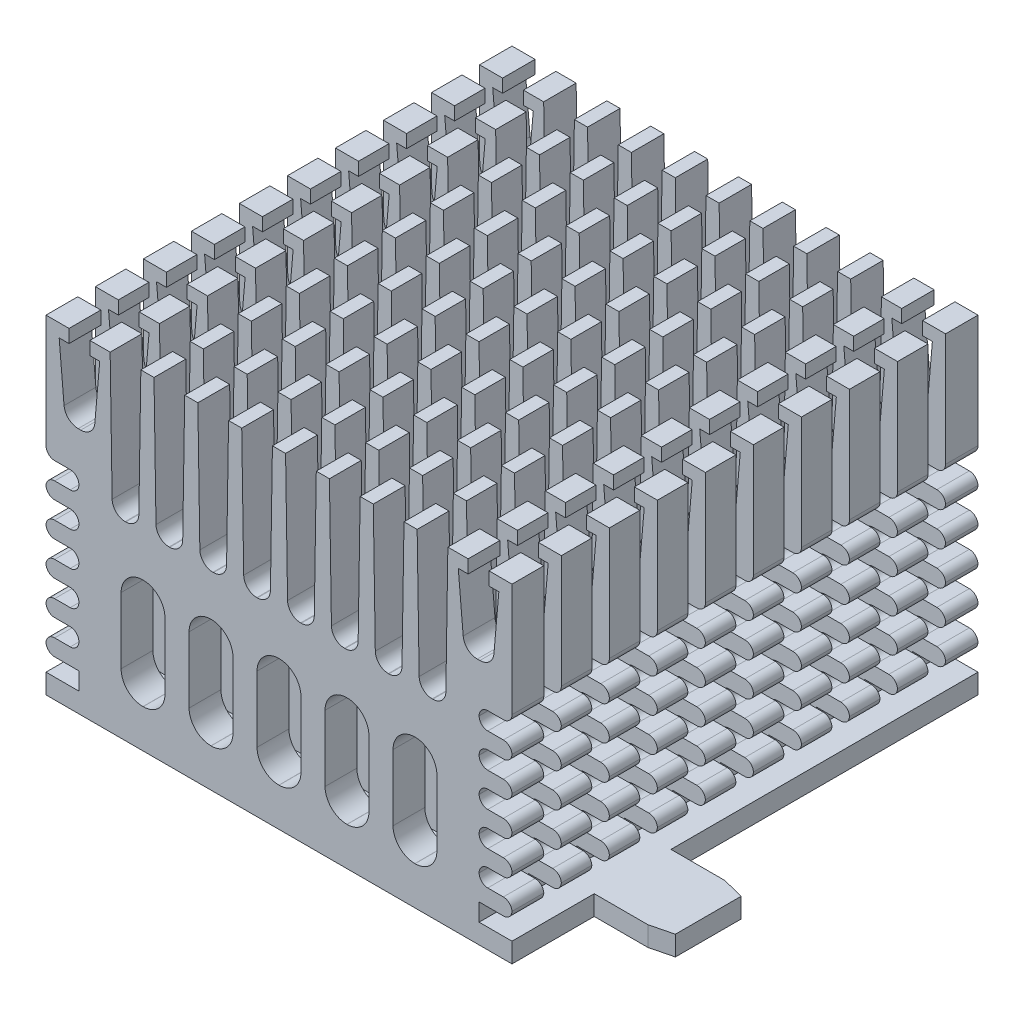
SolidWorks part; units mm, degrees
material "Aleación 1060"
ref_plane "Alzado" through (0, 0, 0) normal (0, 0, 1) x (1, 0, 0)
ref_plane "Planta" through (0, 0, 0) normal (0, 1, 0) x (1, 0, 0)
ref_plane "Vista lateral" through (0, 0, 0) normal (1, 0, 0) x (0, 0, -1)
sketch "Croquis3" plane through (0, 0, 0) normal (0, 1, 0) x (1, 0, 0)
  line L1 (-21.25, 21.25) -> (21.25, 21.25)
  line L2 (-21.25, 21.25) -> (-21.25, -21.25)
  line L3 (-21.25, -21.25) -> (21.25, -21.25)
  line L4 (21.25, 21.25) -> (21.25, -21.25)
  dimension "D1" = 42.5
  dimension "D2" = 42.5
  dimension "D3" = 21.25
  dimension "D4" = 21.25
extrude "Extruir1" add sketch "Croquis3" along normal blind 30
sketch "Croquis4" plane through (0, 0, 21.25) normal (0, 0, 1) x (1, 0, 0)
  line L0 (-19.15, 30) -> (-19.15, 28.8)
  line L1 (-21.25, 30) -> (21.25, 30) construction
  line L2 (-19.15, 28.8) -> (-20.05, 28.8)
  line L3 (-20.05, 28.8) -> (-19.6028, 23.6778)
  line L4 (-18.3177, 22.5) -> (-18.0823, 22.5)
  line L5 (-16.7972, 23.6778) -> (-16.35, 28.8)
  line L6 (-16.35, 28.8) -> (-17.25, 28.8)
  line L7 (-17.25, 28.8) -> (-17.25, 30)
  line L8 (-17.25, 30) -> (-19.15, 30)
  line L9 (-0.6, 30) -> (-0.7816, 18.4713)
  line L10 (-18.2, 30) -> (-18.2, 19.4356) construction
  line L11 (-21.25, 30) -> (-21.25, 0) construction
  line L12 (0, 30) -> (0, 39.1053) construction
  line L13 (-1.9714, 17.3) -> (-2.0286, 17.3)
  line L14 (17.25, 30) -> (19.15, 30)
  line L15 (17.25, 28.8) -> (17.25, 30)
  line L16 (16.35, 28.8) -> (17.25, 28.8)
  line L17 (16.7972, 23.6778) -> (16.35, 28.8)
  line L18 (18.3177, 22.5) -> (18.0823, 22.5)
  line L19 (20.05, 28.8) -> (19.6028, 23.6778)
  line L20 (19.15, 28.8) -> (20.05, 28.8)
  line L21 (19.15, 30) -> (19.15, 28.8)
  line L22 (-3.2184, 18.4713) -> (-3.4, 30)
  line L23 (-3.4, 30) -> (-0.6, 30)
  line L24 (-2, 30) -> (-2, 27.0397) construction
  line L25 (-4.6, 30) -> (-4.7816, 18.4713)
  line L26 (-5.9714, 17.3) -> (-6.0286, 17.3)
  line L27 (-7.2184, 18.4713) -> (-7.4, 30)
  line L28 (-7.4, 30) -> (-4.6, 30)
  line L29 (-6, 30) -> (-6, 27.0397) construction
  line L30 (-8.6, 30) -> (-8.7816, 18.4713)
  line L31 (-9.9714, 17.3) -> (-10.0286, 17.3)
  line L32 (-11.2184, 18.4713) -> (-11.4, 30)
  line L33 (-11.4, 30) -> (-8.6, 30)
  line L34 (-10, 30) -> (-10, 27.0397) construction
  line L35 (-12.6, 30) -> (-12.7816, 18.4713)
  line L36 (-13.9714, 17.3) -> (-14.0286, 17.3)
  line L37 (-15.2184, 18.4713) -> (-15.4, 30)
  line L38 (-15.4, 30) -> (-12.6, 30)
  line L39 (-14, 30) -> (-14, 27.0397) construction
  line L40 (14, 30) -> (14, 27.0397) construction
  line L41 (10, 30) -> (10, 27.0397) construction
  line L42 (6, 30) -> (6, 27.0397) construction
  line L43 (2, 30) -> (2, 27.0397) construction
  line L44 (15.4, 30) -> (12.6, 30)
  line L45 (15.2184, 18.4713) -> (15.4, 30)
  line L46 (13.9714, 17.3) -> (14.0286, 17.3)
  line L47 (12.6, 30) -> (12.7816, 18.4713)
  line L48 (11.4, 30) -> (8.6, 30)
  line L49 (11.2184, 18.4713) -> (11.4, 30)
  line L50 (9.9714, 17.3) -> (10.0286, 17.3)
  line L51 (8.6, 30) -> (8.7816, 18.4713)
  line L52 (7.4, 30) -> (4.6, 30)
  line L53 (7.2184, 18.4713) -> (7.4, 30)
  line L54 (5.9714, 17.3) -> (6.0286, 17.3)
  line L55 (4.6, 30) -> (4.7816, 18.4713)
  line L56 (3.4, 30) -> (0.6, 30)
  line L57 (3.2184, 18.4713) -> (3.4, 30)
  line L58 (1.9714, 17.3) -> (2.0286, 17.3)
  line L59 (0.6, 30) -> (0.7816, 18.4713)
  arc A0 (-19.6028, 23.6778) -> (-18.3177, 22.5) centre (-18.3177, 23.79) ccw
  arc A1 (-18.0823, 22.5) -> (-16.7972, 23.6778) centre (-18.0823, 23.79) ccw
  arc A2 (18.0823, 22.5) -> (16.7972, 23.6778) centre (18.0823, 23.79) cw
  arc A3 (19.6028, 23.6778) -> (18.3177, 22.5) centre (18.3177, 23.79) cw
  arc A4 (-0.7816, 18.4713) -> (-1.9714, 17.3) centre (-1.9714, 18.49) cw
  arc A5 (-2.0286, 17.3) -> (-3.2184, 18.4713) centre (-2.0286, 18.49) cw
  arc A6 (-4.7816, 18.4713) -> (-5.9714, 17.3) centre (-5.9714, 18.49) cw
  arc A7 (-6.0286, 17.3) -> (-7.2184, 18.4713) centre (-6.0286, 18.49) cw
  arc A8 (-8.7816, 18.4713) -> (-9.9714, 17.3) centre (-9.9714, 18.49) cw
  arc A9 (-10.0286, 17.3) -> (-11.2184, 18.4713) centre (-10.0286, 18.49) cw
  arc A10 (-12.7816, 18.4713) -> (-13.9714, 17.3) centre (-13.9714, 18.49) cw
  arc A11 (-14.0286, 17.3) -> (-15.2184, 18.4713) centre (-14.0286, 18.49) cw
  arc A12 (14.0286, 17.3) -> (15.2184, 18.4713) centre (14.0286, 18.49) ccw
  arc A13 (12.7816, 18.4713) -> (13.9714, 17.3) centre (13.9714, 18.49) ccw
  arc A14 (10.0286, 17.3) -> (11.2184, 18.4713) centre (10.0286, 18.49) ccw
  arc A15 (8.7816, 18.4713) -> (9.9714, 17.3) centre (9.9714, 18.49) ccw
  arc A16 (6.0286, 17.3) -> (7.2184, 18.4713) centre (6.0286, 18.49) ccw
  arc A17 (4.7816, 18.4713) -> (5.9714, 17.3) centre (5.9714, 18.49) ccw
  arc A18 (2.0286, 17.3) -> (3.2184, 18.4713) centre (2.0286, 18.49) ccw
  arc A19 (0.7816, 18.4713) -> (1.9714, 17.3) centre (1.9714, 18.49) ccw
  point P17 (-19.5, 22.5)
  point P20 (-16.9, 22.5)
  point P37 (16.9, 22.5)
  point P38 (19.5, 22.5)
  point P45 (-0.8, 17.3)
  point P48 (-3.2, 17.3)
  point P119 (3.2, 17.3)
  point P120 (0.8, 17.3)
  dimension "D9" = 1.29
  dimension "D15" = 1.19
  dimension "D1" = 1.9
  dimension "D2" = 3.7
  dimension "D3" = 1.85
  dimension "D4" = 1.2
  dimension "D5" = 7.5
  dimension "D6" = 2.6
  dimension "D7" = 1.3
  dimension "D8" = 2.1
  dimension "D10" = 2.8
  dimension "D11" = 2.4
  dimension "D12" = 1.2
  dimension "D13" = 12.7
  dimension "D14" = 0.6
extrude "Cortar-Extruir1" cut sketch "Croquis4" against normal blind 55
sketch "Croquis5" plane through (0, 0, 21.25) normal (0, 0, 1) x (1, 0, 0)
  line L0 (-21.25, 30) -> (-21.25, 0) construction
  line L1 (-21.8997, 18.9) -> (-18.25, 18.9)
  line L2 (-21.8997, 18.9) -> (-21.8997, 17.3)
  line L3 (-21.8997, 17.3) -> (-18.25, 17.3)
  line L4 (-18.25, 18.9) -> (-18.25, 17.3)
  line L5 (-21.8997, 15.8) -> (-18.25, 15.8)
  line L6 (-21.8997, 15.8) -> (-21.8997, 14.2)
  line L7 (-21.8997, 14.2) -> (-18.25, 14.2)
  line L8 (-18.25, 15.8) -> (-18.25, 14.2)
  line L9 (-21.8997, 12.7) -> (-18.25, 12.7)
  line L10 (-21.8997, 12.7) -> (-21.8997, 11.1)
  line L11 (-21.8997, 11.1) -> (-18.25, 11.1)
  line L12 (-18.25, 12.7) -> (-18.25, 11.1)
  line L13 (-21.8997, 9.6) -> (-18.25, 9.6)
  line L14 (-21.8997, 9.6) -> (-21.8997, 8)
  line L15 (-21.8997, 8) -> (-18.25, 8)
  line L16 (-18.25, 9.6) -> (-18.25, 8)
  line L17 (-21.8997, 6.5) -> (-18.25, 6.5)
  line L18 (-21.8997, 6.5) -> (-21.8997, 4.9)
  line L19 (-21.8997, 4.9) -> (-18.25, 4.9)
  line L20 (-18.25, 6.5) -> (-18.25, 4.9)
  line L21 (-21.8997, 3.4) -> (-18.25, 3.4)
  line L22 (-21.8997, 3.4) -> (-21.8997, 1.8)
  line L23 (-21.8997, 1.8) -> (-18.25, 1.8)
  line L24 (-18.25, 3.4) -> (-18.25, 1.8)
  line L25 (0, 0) -> (0, -4.9995) construction
  line L26 (18.25, 3.4) -> (18.25, 1.8)
  line L27 (21.8997, 1.8) -> (18.25, 1.8)
  line L28 (21.8997, 3.4) -> (21.8997, 1.8)
  line L29 (21.8997, 3.4) -> (18.25, 3.4)
  line L30 (18.25, 6.5) -> (18.25, 4.9)
  line L31 (21.8997, 4.9) -> (18.25, 4.9)
  line L32 (21.8997, 6.5) -> (21.8997, 4.9)
  line L33 (21.8997, 6.5) -> (18.25, 6.5)
  line L34 (18.25, 9.6) -> (18.25, 8)
  line L35 (21.8997, 8) -> (18.25, 8)
  line L36 (21.8997, 9.6) -> (21.8997, 8)
  line L37 (21.8997, 9.6) -> (18.25, 9.6)
  line L38 (18.25, 12.7) -> (18.25, 11.1)
  line L39 (21.8997, 11.1) -> (18.25, 11.1)
  line L40 (21.8997, 12.7) -> (21.8997, 11.1)
  line L41 (21.8997, 12.7) -> (18.25, 12.7)
  line L42 (18.25, 15.8) -> (18.25, 14.2)
  line L43 (21.8997, 14.2) -> (18.25, 14.2)
  line L44 (21.8997, 15.8) -> (21.8997, 14.2)
  line L45 (21.8997, 15.8) -> (18.25, 15.8)
  line L46 (18.25, 18.9) -> (18.25, 17.3)
  line L47 (21.8997, 17.3) -> (18.25, 17.3)
  line L48 (21.8997, 18.9) -> (21.8997, 17.3)
  line L49 (21.8997, 18.9) -> (18.25, 18.9)
  dimension "D1" = 3
  dimension "D2" = 1.6
  dimension "D3" = 1.5
extrude "Cortar-Extruir2" cut sketch "Croquis5" against normal blind 55
fillet "Redondeo1" radius 0.79 21 edges at (-21.25, 3.4, 0) (-21.25, 4.9, 0) (-18.25, 4.9, 0) (-18.25, 6.5, 0) (-21.25, 6.5, 0) (-21.25, 8, 0) (-18.25, 9.6, 0) (-18.25, 8, 0) (-21.25, 9.6, 0) (-21.25, 11.1, 0) (-18.25, 12.7, 0) (-18.25, 11.1, 0) (-21.25, 12.7, 0) (-21.25, 14.2, 0) (-18.25, 14.2, 0) (-18.25, 15.8, 0) (-21.25, 15.8, 0) (-21.25, 17.3, 0) (-21.25, 18.9, 0) (-18.25, 17.3, 0) (-18.25, 18.9, 0)
fillet "Redondeo2" radius 0.79 21 edges at (21.25, 3.4, 0) (21.25, 4.9, 0) (18.25, 4.9, 0) (18.25, 6.5, 0) (21.25, 6.5, 0) (21.25, 8, 0) (18.25, 8, 0) (18.25, 9.6, 0) (21.25, 9.6, 0) (21.25, 11.1, 0) (18.25, 11.1, 0) (18.25, 12.7, 0) (21.25, 12.7, 0) (21.25, 14.2, 0) (18.25, 14.2, 0) (18.25, 15.8, 0) (21.25, 15.8, 0) (21.25, 17.3, 0) (18.25, 17.3, 0) (18.25, 18.9, 0) (21.25, 18.9, 0)
sketch "Croquis7" plane through (0, 0, 21.25) normal (0, 0, 1) x (1, 0, 0)
  line L0 (0, 0) -> (0, -2.1081) construction
  line L1 (-0.01, 13.5) -> (0.01, 13.5)
  line L2 (-2, 11.51) -> (-2, 5.49)
  line L3 (-0.01, 3.5) -> (0.01, 3.5)
  line L4 (2, 11.51) -> (2, 5.49)
  line L5 (-21.25, 0) -> (21.25, 0) construction
  line L6 (6.19, 13.5) -> (6.21, 13.5)
  line L7 (4.2, 11.51) -> (4.2, 5.49)
  line L8 (6.19, 3.5) -> (6.21, 3.5)
  line L9 (8.2, 11.51) -> (8.2, 5.49)
  line L10 (12.39, 13.5) -> (12.41, 13.5)
  line L11 (10.4, 11.51) -> (10.4, 5.49)
  line L12 (12.39, 3.5) -> (12.41, 3.5)
  line L13 (14.4, 11.51) -> (14.4, 5.49)
  line L14 (-14.4, 11.51) -> (-14.4, 5.49)
  line L15 (-12.39, 3.5) -> (-12.41, 3.5)
  line L16 (-10.4, 11.51) -> (-10.4, 5.49)
  line L17 (-12.39, 13.5) -> (-12.41, 13.5)
  line L18 (-8.2, 11.51) -> (-8.2, 5.49)
  line L19 (-6.19, 3.5) -> (-6.21, 3.5)
  line L20 (-4.2, 11.51) -> (-4.2, 5.49)
  line L21 (-6.19, 13.5) -> (-6.21, 13.5)
  arc A0 (0.01, 3.5) -> (2, 5.49) centre (0.01, 5.49) ccw
  arc A1 (-2, 5.49) -> (-0.01, 3.5) centre (-0.01, 5.49) ccw
  arc A2 (-0.01, 13.5) -> (-2, 11.51) centre (-0.01, 11.51) ccw
  arc A3 (0.01, 13.5) -> (2, 11.51) centre (0.01, 11.51) cw
  arc A4 (6.21, 3.5) -> (8.2, 5.49) centre (6.21, 5.49) ccw
  arc A5 (4.2, 5.49) -> (6.19, 3.5) centre (6.19, 5.49) ccw
  arc A6 (6.19, 13.5) -> (4.2, 11.51) centre (6.19, 11.51) ccw
  arc A7 (6.21, 13.5) -> (8.2, 11.51) centre (6.21, 11.51) cw
  arc A8 (12.41, 3.5) -> (14.4, 5.49) centre (12.41, 5.49) ccw
  arc A9 (10.4, 5.49) -> (12.39, 3.5) centre (12.39, 5.49) ccw
  arc A10 (12.39, 13.5) -> (10.4, 11.51) centre (12.39, 11.51) ccw
  arc A11 (12.41, 13.5) -> (14.4, 11.51) centre (12.41, 11.51) cw
  arc A12 (-12.41, 13.5) -> (-14.4, 11.51) centre (-12.41, 11.51) ccw
  arc A13 (-12.39, 13.5) -> (-10.4, 11.51) centre (-12.39, 11.51) cw
  arc A14 (-10.4, 5.49) -> (-12.39, 3.5) centre (-12.39, 5.49) cw
  arc A15 (-12.41, 3.5) -> (-14.4, 5.49) centre (-12.41, 5.49) cw
  arc A16 (-6.21, 13.5) -> (-8.2, 11.51) centre (-6.21, 11.51) ccw
  arc A17 (-6.19, 13.5) -> (-4.2, 11.51) centre (-6.19, 11.51) cw
  arc A18 (-4.2, 5.49) -> (-6.19, 3.5) centre (-6.19, 5.49) cw
  arc A19 (-6.21, 3.5) -> (-8.2, 5.49) centre (-6.21, 5.49) cw
  dimension "D5" = 1.99
  dimension "D1" = 10
  dimension "D2" = 4
  dimension "D3" = 2
  dimension "D4" = 3.5
extrude "Cortar-Extruir3" cut sketch "Croquis7" against normal blind 55
sketch "Croquis8" plane through (21.25, 0, 0) normal (1, 0, 0) x (0, 0, -1)
  line L0 (-21.25, 30) -> (-21.25, 19.69) construction
  line L1 (-18.35, 32.5522) -> (-16.75, 32.5522)
  line L2 (-18.35, 32.5522) -> (-18.35, 2.5)
  line L3 (-18.35, 2.5) -> (-16.75, 2.5)
  line L4 (-16.75, 32.5522) -> (-16.75, 2.5)
  line L5 (-21.25, 0) -> (21.25, 0) construction
  line L6 (-13.97, 32.5522) -> (-12.37, 32.5522)
  line L7 (-13.97, 32.5522) -> (-13.97, 2.5)
  line L8 (-13.97, 2.5) -> (-12.37, 2.5)
  line L9 (-12.37, 32.5522) -> (-12.37, 2.5)
  line L10 (-9.59, 32.5522) -> (-7.99, 32.5522)
  line L11 (-9.59, 32.5522) -> (-9.59, 2.5)
  line L12 (-9.59, 2.5) -> (-7.99, 2.5)
  line L13 (-7.99, 32.5522) -> (-7.99, 2.5)
  line L14 (-5.21, 32.5522) -> (-3.61, 32.5522)
  line L15 (-5.21, 32.5522) -> (-5.21, 2.5)
  line L16 (-5.21, 2.5) -> (-3.61, 2.5)
  line L17 (-3.61, 32.5522) -> (-3.61, 2.5)
  line L18 (-0.83, 32.5522) -> (0.77, 32.5522)
  line L19 (-0.83, 32.5522) -> (-0.83, 2.5)
  line L20 (-0.83, 2.5) -> (0.77, 2.5)
  line L21 (0.77, 32.5522) -> (0.77, 2.5)
  line L22 (3.55, 32.5522) -> (5.15, 32.5522)
  line L23 (3.55, 32.5522) -> (3.55, 2.5)
  line L24 (3.55, 2.5) -> (5.15, 2.5)
  line L25 (5.15, 32.5522) -> (5.15, 2.5)
  line L26 (7.93, 32.5522) -> (9.53, 32.5522)
  line L27 (7.93, 32.5522) -> (7.93, 2.5)
  line L28 (7.93, 2.5) -> (9.53, 2.5)
  line L29 (9.53, 32.5522) -> (9.53, 2.5)
  line L30 (12.31, 32.5522) -> (13.91, 32.5522)
  line L31 (12.31, 32.5522) -> (12.31, 2.5)
  line L32 (12.31, 2.5) -> (13.91, 2.5)
  line L33 (13.91, 32.5522) -> (13.91, 2.5)
  line L34 (16.69, 32.5522) -> (18.29, 32.5522)
  line L35 (16.69, 32.5522) -> (16.69, 2.5)
  line L36 (16.69, 2.5) -> (18.29, 2.5)
  line L37 (18.29, 32.5522) -> (18.29, 2.5)
  dimension "D1" = 1.6
  dimension "D2" = 2.9
  dimension "D3" = 2.5
extrude "Cortar-Extruir4" cut sketch "Croquis8" against normal blind 55
sketch "Croquis9" plane through (0, 0, 0) normal (0, -1, 0) x (1, 0, 0)
  line L0 (-21.25, -12.31) -> (-21.25, -9.53) construction
  line L1 (-28.15, -13.75) -> (-21.25, -13.75)
  line L2 (-28.15, -13.75) -> (-28.15, -6.75)
  line L3 (-28.15, -6.75) -> (-21.25, -6.75)
  line L4 (-21.25, -13.75) -> (-21.25, -6.75)
  line L5 (21.25, -21.25) -> (21.25, 21.25) construction
  line L6 (21.25, 13.75) -> (28.15, 13.75)
  line L7 (21.25, 13.75) -> (21.25, 6.75)
  line L8 (21.25, 6.75) -> (28.15, 6.75)
  line L9 (28.15, 13.75) -> (28.15, 6.75)
  dimension "D1" = 7
  dimension "D2" = 6.9
  dimension "D3" = 7.5
  dimension "D4" = 7.5
  dimension "D5" = 7
  dimension "D6" = 6.9
extrude "Extruir2" add sketch "Croquis9" against normal blind 1.8
chamfer "Chaflán1" distance 0.5 angle 76 1 edges at (28.15, 0.9, 13.75) first distance on face at (28.15, 0.9, 10.25)
chamfer "Chaflán2" distance 0.5 angle 76 1 edges at (28.15, 0.9, 6.75) first distance on face at (28.15, 0.9, 10)
chamfer "Chaflán3" distance 0.5 angle 76 1 edges at (-28.15, 0.9, -6.75) first distance on face at (-28.15, 0.9, -10.25)
chamfer "Chaflán4" distance 0.5 angle 76 1 edges at (-28.15, 0.9, -13.75) first distance on face at (-28.15, 0.9, -10.5)
